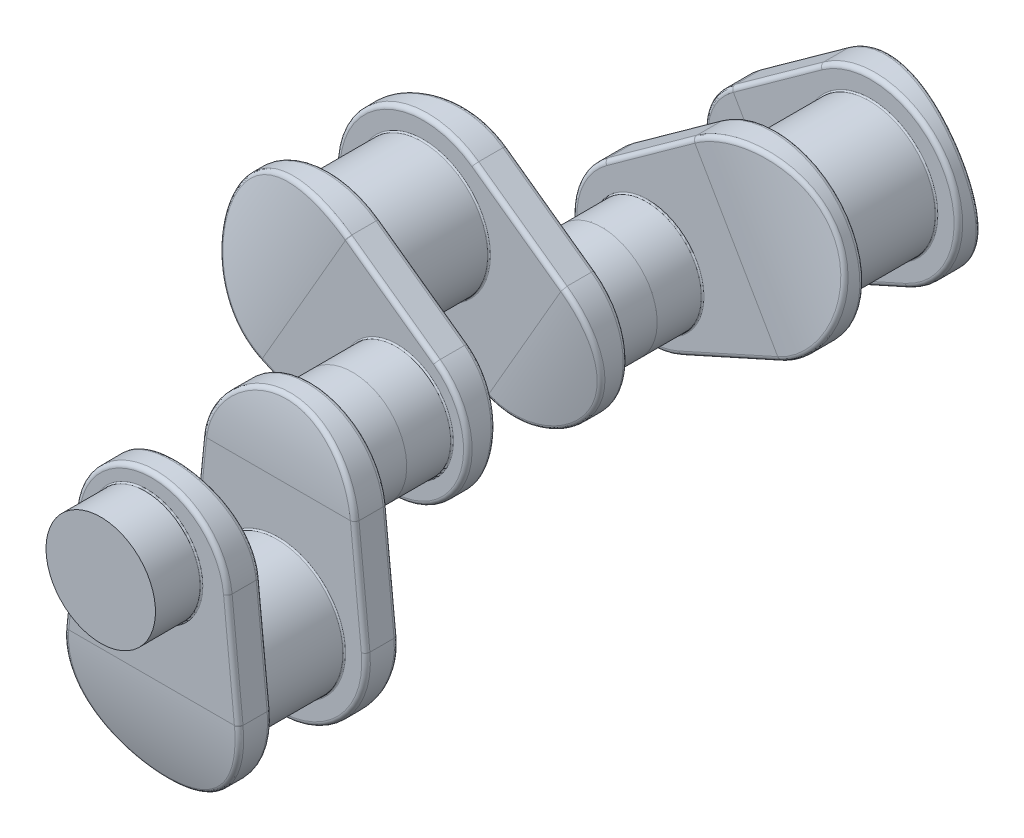
SolidWorks part; units mm, degrees
note: '?' marks a value the reader was unsure of.
material "Alloy Steel"
ref_plane "Front Plane" through (0, 0, 0) normal (0, 0, 1) x (1, 0, 0)
ref_plane "Top Plane" through (0, 0, 0) normal (0, 1, 0) x (1, 0, 0)
ref_plane "Right Plane" through (0, 0, 0) normal (1, 0, 0) x (0, 0, -1)
sketch "Sketch1" plane through (0, 0, 0) normal (0, 0, 1) x (1, 0, 0)
  circle A0 centre (0, 0) radius 38.1
  dimension "D1" = 76.2
extrude "Boss-Extrude1" add sketch "Sketch1" along normal blind 27.31
sketch "Sketch2" plane through (0, 0, 27.31) normal (0, 0, 1) x (1, 0, 0)
  line L0 (-44.2272, 67.945) -> (-50.5454, 5.08)
  line L1 (44.2272, 67.945) -> (50.5454, 5.08)
  arc A0 (-50.5454, 5.08) -> (50.5454, 5.08) centre (0, 0) ccw
  circle A2 centre (0, 0) radius 38.1 construction
  arc A3 (44.2272, 67.945) -> (-44.2272, 67.945) centre (0, 63.5) ccw
  dimension "D1" = 12.7
  dimension "D3" = 63.5
extrude "Boss-Extrude2" add sketch "Sketch2" along normal blind 19
sketch "Sketch4" plane through (0, 0, 46.31) normal (0, 0, 1) x (1, 0, 0)
  circle A0 centre (-2.8235, 65.9452) radius 31.75
  dimension "D1" = 63.5
extrude "Boss-Extrude3" add sketch "Sketch4" along normal blind 26.67
sketch "Sketch5" plane through (0, 0, 0) normal (1, 0, 0) x (0, 0, -1)
  line L0 (-46.31, -50.8) -> (-27.31, -50.8) construction
  line L1 (-46.31, 5.08) -> (-64.227, 5.08)
  line L2 (-64.227, 5.08) -> (-64.227, -50.8)
  line L3 (-64.227, -50.8) -> (-36.81, -50.8)
  line L4 (-27.31, 107.95) -> (-46.31, 107.95) construction
  line L5 (-32.31, 107.95) -> (-32.31, 128.8994)
  line L6 (-32.31, 128.8994) -> (-11.5534, 128.8994)
  line L7 (-11.5534, 128.8994) -> (-11.5534, 67.945)
  line L8 (-11.5534, 67.945) -> (-27.31, 67.945)
  arc A0 (-46.31, 5.08) -> (-36.81, -50.8) centre (122.69, 5.0637) ccw
  arc A1 (-32.31, 107.95) -> (-27.31, 67.945) centre (-196.3081, 67.1378) cw
  dimension "D1" = 169
  dimension "D3" = 169
  dimension "D2" = 5
extrude "Cut-Extrude1" cut sketch "Sketch5" against normal through all both and the other way through all
fillet "Fillet1" radius 2.5 10 edges at (47.3863, 36.5125, 27.31) (0, -50.8, 27.31) (-47.3863, 36.5125, 27.31) (47.3863, 36.5125, 46.31) (50.5462, 5.0718, 46.31) (0.2541, -50.7994, 36.8102) (-50.5462, 5.0718, 46.31) (-47.3863, 36.5125, 46.31) (5.8292, 107.5661, 32.2149) (0, 107.95, 46.31)
fillet "Fillet2" radius 0.8 2 edges at (38.1, 0, 27.31) (28.9265, 65.9452, 46.31)
mirror "Mirror5" about plane through (0, 0, 0) normal (0, 0, 1) of bodies 104
pattern_linear "LPattern1" count 3 spacing 145.36 along (0, 0, -1) of bodies 105
ref_axis "Axis1" through (-2.8235, 65.9452, 131.779) along (0, 0, -1)?
move or copy body "Body-Move/Copy1" bodies to move or copy 106 copy no rotation origin (-2.8235, 65.9452, 0) rotation axis (0, 0, -1) rotation angle 120
move or copy body "Body-Move/Copy2" bodies to move or copy 107 copy no rotation origin (-2.8235, 65.9452, 0) rotation axis (0, 0, 1) rotation angle 120
